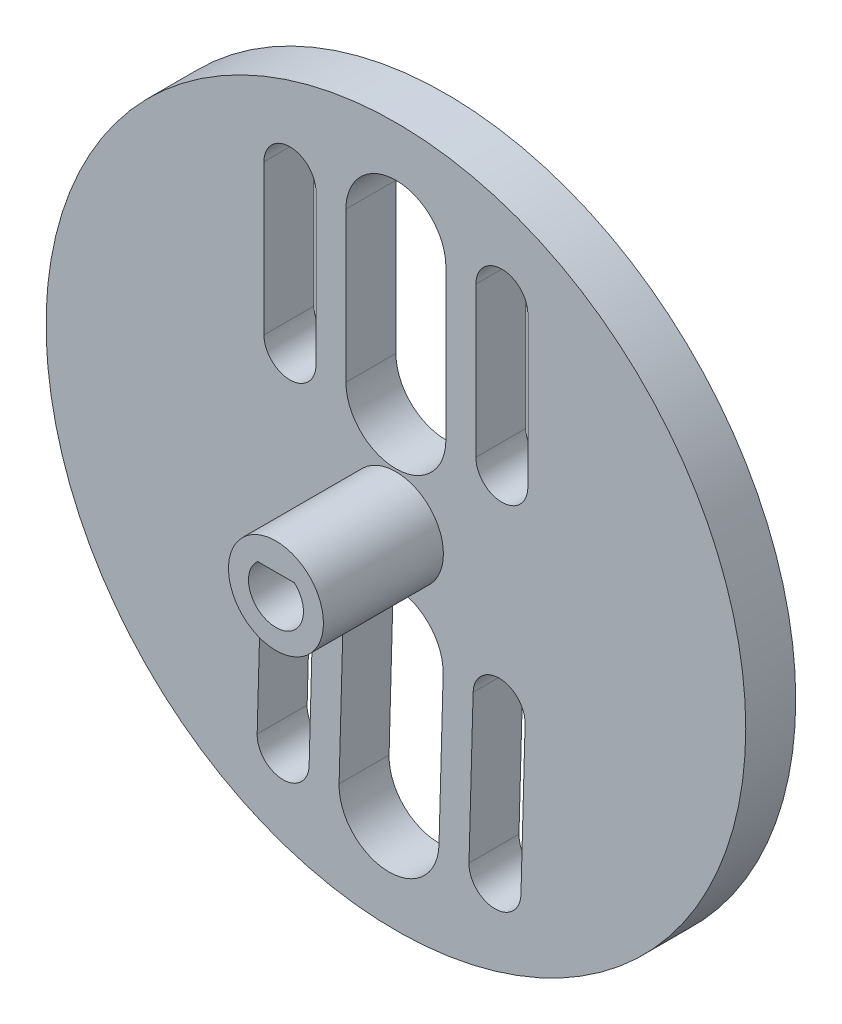
SolidWorks part; units mm, degrees
ref_plane "Plan de face" through (0, 0, 0) normal (0, 0, 1) x (1, 0, 0)
ref_plane "Plan de dessus" through (0, 0, 0) normal (0, 1, 0) x (1, 0, 0)
ref_plane "Plan de droite" through (0, 0, 0) normal (1, 0, 0) x (0, 0, -1)
sketch "Esquisse1" plane through (0, 0, 0) normal (0, 0, 1) x (1, 0, 0)
  line L0 (0, 0) -> (0, 35) construction
  line L1 (-5, 10) -> (5, 10)
  line L2 (-5, 10) -> (-5, 25)
  line L3 (-5, 25) -> (5, 25)
  line L4 (5, 10) -> (5, 25)
  line L5 (10.6, 25) -> (10.6, 10) construction
  line L6 (13.2, 25) -> (13.2, 10)
  line L7 (8, 25) -> (8, 10)
  line L8 (0, 10) -> (31.7532, 10) construction
  line L9 (-10.6, 25) -> (-10.6, 10) construction
  line L10 (-13.2, 25) -> (-13.2, 10)
  line L11 (-8, 25) -> (-8, 10)
  line L12 (4.7262, -10.4207) -> (4.3125, -25.415)
  line L13 (4.7262, -10.4207) -> (-5.27, -10.1449)
  line L14 (-5.27, -10.1449) -> (-5.6837, -25.1392)
  line L15 (4.3125, -25.415) -> (-5.6837, -25.1392)
  line L16 (12.5094, -25.6412) -> (12.9231, -10.6469)
  line L17 (7.3113, -25.4978) -> (7.7251, -10.5035)
  line L18 (-8.6826, -25.0564) -> (-8.2688, -10.0622)
  line L19 (-13.8806, -24.913) -> (-13.4669, -9.9187)
  line L20 (-11.2816, -24.9847) -> (-10.8679, -9.9904) construction
  line L21 (9.9103, -25.5695) -> (10.3241, -10.5752) construction
  circle A0 centre (0, 0) radius 35
  circle A1 centre (0, 25) radius 5
  circle A2 centre (0, 10) radius 5
  arc A3 (13.2, 25) -> (8, 25) centre (10.6, 25) ccw
  arc A4 (8, 10) -> (13.2, 10) centre (10.6, 10) ccw
  arc A5 (-13.2, 25) -> (-8, 25) centre (-10.6, 25) cw
  arc A6 (-8, 10) -> (-13.2, 10) centre (-10.6, 10) cw
  circle A7 centre (-0.2719, -10.2828) radius 5
  circle A8 centre (-0.6856, -25.2771) radius 5
  arc A9 (7.7251, -10.5035) -> (12.9231, -10.6469) centre (10.3241, -10.5752) cw
  arc A10 (12.5094, -25.6412) -> (7.3113, -25.4978) centre (9.9103, -25.5695) cw
  arc A11 (-13.8806, -24.913) -> (-8.6826, -25.0564) centre (-11.2816, -24.9847) ccw
  arc A12 (-8.2688, -10.0622) -> (-13.4669, -9.9187) centre (-10.8679, -9.9904) ccw
  point P13 (10.6, 17.5)
  point P22 (-10.6, 17.5)
  point P40 (-11.0747, -17.4876)
  point P47 (10.1172, -18.0723)
  point P52 (0.0039, -0.1433)
  dimension "D1" = 70
  dimension "D2" = 10
  dimension "D3" = 10
  dimension "D7" = 2.6
  dimension "D8" = 15
  dimension "D4" = 10
  dimension "D5" = 25
  dimension "D6" = 3
  dimension "D9" = 2
extrude "Boss.-Extru.1" add sketch "Esquisse1" along normal blind 5 contours A0 A12 L18 A11 L19 A8 L14 A7 L12 A4 L7 A3 L6 A2 L2 A1 L4 L11 A6 L10 A5 L16 A10 L17 A9 region at (0.0683, 0.0399, 0)
sketch "Esquisse2" plane through (0, 0, 5) normal (0, 0, 1) x (1, 0, 0)
  line L0 (-1.833, 2.05) -> (1.833, 2.05)
  line L7 (0, 2.05) -> (0, 2.75) construction
  circle A0 centre (0, 0) radius 2.75
  dimension "D1" = 5.5
  dimension "D2" = 0.7
  dimension "D3" = 2.05
extrude "Enlèv. mat.-Extru.1" cut sketch "Esquisse2" against normal up to next contours L0 A0 region at (0, -0.1866, 5)
sketch "Esquisse3" plane through (0, 0, 5) normal (0, 0, 1) x (1, 0, 0)
  line L0 (-1.833, 2.05) -> (1.833, 2.05)
  circle A0 centre (0, 0) radius 4.75
  arc A1 (-1.833, 2.05) -> (1.833, 2.05) centre (0, 0) ccw construction
  circle A2 centre (0, 0) radius 2.6
  arc M27 (1.833, 2.05) -> (-1.833, 2.05) centre (0, 0) cw
  line M28 (-1.833, 2.05) -> (1.833, 2.05)
  dimension "D1" = 2
extrude "Boss.-Extru.3" add sketch "Esquisse3" along normal blind 12 contours A2 M28 | A0 A2 M27 region at (0, 2.2721, 5) region at (-4.6156, 0, 5)
